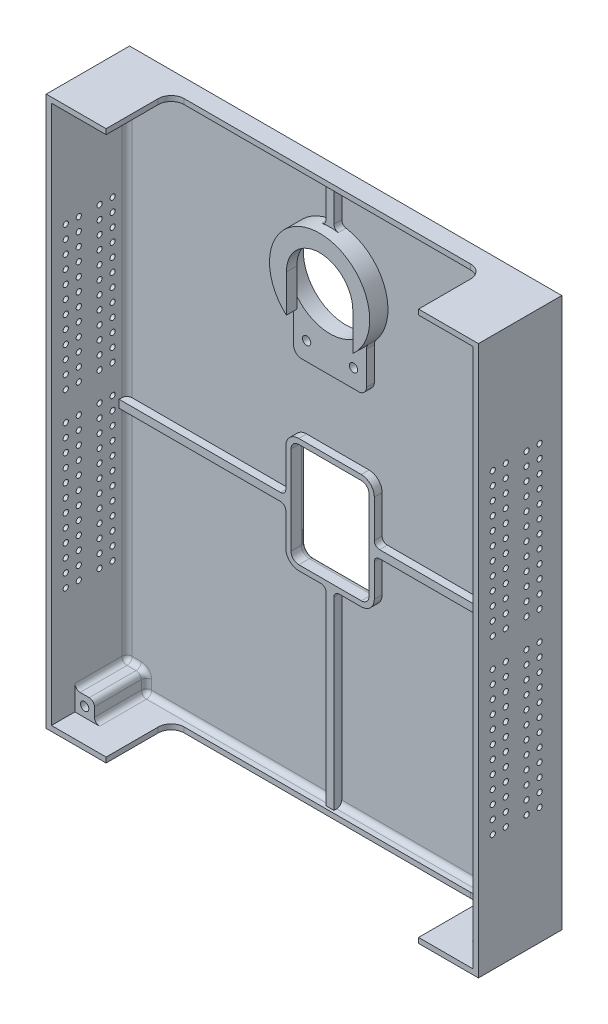
SolidWorks part; units mm, degrees
ref_plane "Front Plane" through (0, 0, 0) normal (0, 0, 1) x (1, 0, 0)
ref_plane "Top Plane" through (0, 0, 0) normal (0, 1, 0) x (1, 0, 0)
ref_plane "Right Plane" through (0, 0, 0) normal (1, 0, 0) x (0, 0, -1)
ref_plane "Plane1" through (0, 0, -1) normal (0, 0, 1) x (1, 0, 0)
sketch "Sketch5" plane through (0, 0, -1) normal (0, 0, 1) x (1, 0, 0)
  line L0 (100, 83.2573) -> (100, -169.2647) construction
  line L2 (17, 83.2573) -> (17, -127.7573)
  line L3 (17, -127.7573) -> (183, -127.7573)
  line L4 (183, 83.2573) -> (183, -127.7573)
  line L5 (17, 83.2573) -> (183, 83.2573)
  circle A0 centre (100, 48.2573) radius 16.25
  point P17 (45, 83.2573)
  dimension "D1" = 166
  dimension "D2" = 83
extrude "Boss-Extrude5" add sketch "Sketch5" along normal blind 3
sketch "Sketch6" plane through (0, 0, 2) normal (0, 0, 1) x (1, 0, 0)
  line L0 (116.25, 48.2573) -> (83.75, 48.2573) construction
  line L2 (86, 35.0451) -> (86, 18.2573)
  line L3 (86, 18.2573) -> (114, 18.2573)
  line L4 (114, 35.0451) -> (114, 18.2573)
  line L5 (100, 48.2573) -> (100, 52.872) construction
  circle A1 centre (100, 48.2573) radius 16.25
  arc A2 (114, 35.0451) -> (86, 35.0451) centre (100, 48.2573) ccw
  circle A6 centre (100, 48.2573) radius 16.25 construction
extrude "Boss-Extrude6" add sketch "Sketch6" along normal blind 3
sketch "Sketch7" plane through (0, 0, 5) normal (0, 0, 1) x (1, 0, 0)
  line L0 (112.75, 33.8351) -> (112.75, 48.2573)
  line L2 (87.25, 48.2573) -> (87.25, 33.8351)
  line L3 (100, 64.5073) -> (100, 48.2573) construction
  line L4 (100, 48.2573) -> (116.25, 48.2573) construction
  arc A8 (112.75, 33.8351) -> (87.25, 33.8351) centre (100, 48.2573) ccw
  circle A9 centre (100, 48.2573) radius 19.25 construction
  circle A10 centre (100, 48.2573) radius 16.25 construction
  circle A12 centre (100, 48.2573) radius 12.75
  arc A13 (112.75, 48.2573) -> (87.25, 48.2573) centre (100, 48.2573) ccw
  dimension "D1" = 1
extrude "Boss-Extrude7" add sketch "Sketch7" along normal blind 4
sketch "Sketch8" plane through (0, 0, 2) normal (0, 0, 1) x (1, 0, 0)
  line L4 (17, -127.7573) -> (183, -127.7573)
  line L5 (183, -127.7573) -> (183, 83.2573)
  line L6 (183, 83.2573) -> (17, 83.2573)
  line L7 (17, 83.2573) -> (17, -127.7573)
  line L8 (17, -127.7573) -> (183, -127.7573)
  line L9 (183, -127.7573) -> (183, 83.2573)
  line L10 (183, 83.2573) -> (17, 83.2573)
  line L11 (17, 83.2573) -> (17, -127.7573)
  line L12 (19, -125.7573) -> (181, -125.7573)
  line L13 (181, -125.7573) -> (181, 81.2573)
  line L14 (181, 81.2573) -> (19, 81.2573)
  line L15 (19, 81.2573) -> (19, -125.7573)
  dimension "D1" = 0
  dimension "D2" = 2
extrude "Boss-Extrude8" add sketch "Sketch8" along normal blind 29
fillet "Fillet2" radius 3 4 edges at (114, 18.2573, 3.5) (114, 35.0451, 3.5) (86, 18.2573, 3.5) (86, 35.0451, 3.5)
sketch "Sketch9" plane through (0, 0, 5) normal (0, 0, 1) x (1, 0, 0)
  line L0 (100, 48.2573) -> (100, 25.2573) construction
  line L1 (91, 25.2573) -> (109, 25.2573) construction
  line L2 (100, 25.2573) -> (100, 23.2329) construction
  circle A0 centre (91, 25.2573) radius 1.6
  circle A1 centre (109, 25.2573) radius 1.6
extrude "Cut-Extrude1" cut sketch "Sketch9" against normal up to surface (6 mm away) up to face at (100, -22.25, -1)
sketch "Sketch12" plane through (183, 0, 0) normal (1, 0, 0) x (0, 0, -1)
  circle A0 centre (-12.5, -16.7427) radius 1
  circle A1 centre (-7.5, -16.7427) radius 1
  circle A2 centre (-7.5, -11.7427) radius 1
  circle A3 centre (-7.5, -6.7427) radius 1
  circle A4 centre (-7.5, -1.7427) radius 1
  circle A5 centre (-7.5, 3.2573) radius 1
  circle A6 centre (-7.5, 8.2573) radius 1
  circle A7 centre (-7.5, 13.2573) radius 1
  circle A8 centre (-7.5, 18.2573) radius 1
  circle A9 centre (-7.5, 23.2573) radius 1
  circle A10 centre (-7.5, 28.2573) radius 1
  circle A11 centre (-7.5, 33.2573) radius 1
  circle A12 centre (-7.5, 38.2573) radius 1
  circle A13 centre (-12.5, -11.7427) radius 1
  circle A14 centre (-12.5, -6.7427) radius 1
  circle A15 centre (-12.5, -1.7427) radius 1
  circle A16 centre (-12.5, 3.2573) radius 1
  circle A17 centre (-12.5, 8.2573) radius 1
  circle A18 centre (-12.5, 13.2573) radius 1
  circle A19 centre (-12.5, 18.2573) radius 1
  circle A20 centre (-12.5, 23.2573) radius 1
  circle A21 centre (-12.5, 28.2573) radius 1
  circle A22 centre (-12.5, 33.2573) radius 1
  circle A23 centre (-12.5, 38.2573) radius 1
  circle A24 centre (-12.5, -82.7573) radius 1
  circle A25 centre (-12.5, -77.7573) radius 1
  circle A26 centre (-12.5, -72.7573) radius 1
  circle A27 centre (-12.5, -67.7573) radius 1
  circle A28 centre (-12.5, -62.7573) radius 1
  circle A29 centre (-12.5, -57.7573) radius 1
  circle A30 centre (-12.5, -52.7573) radius 1
  circle A31 centre (-12.5, -47.7573) radius 1
  circle A32 centre (-12.5, -42.7573) radius 1
  circle A33 centre (-12.5, -37.7573) radius 1
  circle A34 centre (-12.5, -32.7573) radius 1
  circle A35 centre (-7.5, -82.7573) radius 1
  circle A36 centre (-7.5, -77.7573) radius 1
  circle A37 centre (-7.5, -72.7573) radius 1
  circle A38 centre (-7.5, -67.7573) radius 1
  circle A39 centre (-7.5, -62.7573) radius 1
  circle A40 centre (-7.5, -57.7573) radius 1
  circle A41 centre (-7.5, -52.7573) radius 1
  circle A42 centre (-7.5, -47.7573) radius 1
  circle A43 centre (-7.5, -42.7573) radius 1
  circle A44 centre (-7.5, -37.7573) radius 1
  circle A45 centre (-7.5, -32.7573) radius 1
  circle A46 centre (-7.5, -27.7573) radius 1
  circle A47 centre (-12.5, -27.7573) radius 1
  circle A48 centre (-20.5, -27.7573) radius 1
  circle A49 centre (-25.5, -27.7573) radius 1
  circle A50 centre (-25.5, -32.7573) radius 1
  circle A51 centre (-25.5, -37.7573) radius 1
  circle A52 centre (-25.5, -42.7573) radius 1
  circle A53 centre (-25.5, -47.7573) radius 1
  circle A54 centre (-25.5, -52.7573) radius 1
  circle A55 centre (-25.5, -57.7573) radius 1
  circle A56 centre (-25.5, -62.7573) radius 1
  circle A57 centre (-25.5, -67.7573) radius 1
  circle A58 centre (-25.5, -72.7573) radius 1
  circle A59 centre (-25.5, -77.7573) radius 1
  circle A60 centre (-25.5, -82.7573) radius 1
  circle A61 centre (-20.5, -32.7573) radius 1
  circle A62 centre (-20.5, -37.7573) radius 1
  circle A63 centre (-20.5, -42.7573) radius 1
  circle A64 centre (-20.5, -47.7573) radius 1
  circle A65 centre (-20.5, -52.7573) radius 1
  circle A66 centre (-20.5, -57.7573) radius 1
  circle A67 centre (-20.5, -62.7573) radius 1
  circle A68 centre (-20.5, -67.7573) radius 1
  circle A69 centre (-20.5, -72.7573) radius 1
  circle A70 centre (-20.5, -77.7573) radius 1
  circle A71 centre (-20.5, -82.7573) radius 1
  circle A72 centre (-20.5, 38.2573) radius 1
  circle A73 centre (-20.5, 33.2573) radius 1
  circle A74 centre (-20.5, 28.2573) radius 1
  circle A75 centre (-20.5, 23.2573) radius 1
  circle A76 centre (-20.5, 18.2573) radius 1
  circle A77 centre (-20.5, 13.2573) radius 1
  circle A78 centre (-20.5, 8.2573) radius 1
  circle A79 centre (-20.5, 3.2573) radius 1
  circle A80 centre (-20.5, -1.7427) radius 1
  circle A81 centre (-20.5, -6.7427) radius 1
  circle A82 centre (-20.5, -11.7427) radius 1
  circle A83 centre (-25.5, 38.2573) radius 1
  circle A84 centre (-25.5, 33.2573) radius 1
  circle A85 centre (-25.5, 28.2573) radius 1
  circle A86 centre (-25.5, 23.2573) radius 1
  circle A87 centre (-25.5, 18.2573) radius 1
  circle A88 centre (-25.5, 13.2573) radius 1
  circle A89 centre (-25.5, 8.2573) radius 1
  circle A90 centre (-25.5, 3.2573) radius 1
  circle A91 centre (-25.5, -1.7427) radius 1
  circle A92 centre (-25.5, -6.7427) radius 1
  circle A93 centre (-25.5, -11.7427) radius 1
  circle A94 centre (-25.5, -16.7427) radius 1
  circle A95 centre (-20.5, -16.7427) radius 1
  dimension "D1" = 2
  dimension "D2" = 12
extrude "Cut-Extrude4" cut sketch "Sketch12" against normal up to surface (2 mm away) up to face at (181, -22.25, 16.5)
sketch "Sketch13" plane through (0, 0, -1) normal (0, 0, -1) x (-1, 0, 0)
  line L0 (-183, -30.7808) -> (-100, -30.7808) construction
  line L1 (-183, -127.7573) -> (-183, 83.2573) construction
  line L6 (-100, 83.2573) -> (-100, -30.7808) construction
  line L7 (-183, 83.2573) -> (-17, 83.2573) construction
  line L14 (-85, -47.7808) -> (-85, -13.7808)
  line L15 (-88, -10.7808) -> (-112, -10.7808)
  line L16 (-115, -13.7808) -> (-115, -47.7808)
  line L17 (-112, -50.7808) -> (-88, -50.7808)
  circle A1 centre (-100, -30.7808) radius 9 construction
  arc A15 (-88, -50.7808) -> (-85, -47.7808) centre (-88, -47.7808) ccw
  arc A16 (-85, -13.7808) -> (-88, -10.7808) centre (-88, -13.7808) ccw
  arc A17 (-112, -10.7808) -> (-115, -13.7808) centre (-112, -13.7808) ccw
  arc A18 (-115, -47.7808) -> (-112, -50.7808) centre (-112, -47.7808) ccw
extrude "Cut-Extrude5" cut sketch "Sketch13" against normal blind 3
sketch "Sketch14" plane through (17, 0, 0) normal (-1, 0, 0) x (0, 0, 1)
  circle A1 centre (12.5, -82.7573) radius 1
  circle A2 centre (12.5, -82.7573) radius 1
  circle A3 centre (12.5, -16.7427) radius 1
  circle A4 centre (12.5, -16.7427) radius 1
  circle A5 centre (7.5, 18.2573) radius 1
  circle A6 centre (7.5, 18.2573) radius 1
  circle A7 centre (7.5, 13.2573) radius 1
  circle A8 centre (7.5, 13.2573) radius 1
  circle A9 centre (7.5, 8.2573) radius 1
  circle A10 centre (7.5, 8.2573) radius 1
  circle A11 centre (7.5, 3.2573) radius 1
  circle A12 centre (7.5, 3.2573) radius 1
  circle A13 centre (7.5, -1.7427) radius 1
  circle A14 centre (7.5, -1.7427) radius 1
  circle A15 centre (7.5, -6.7427) radius 1
  circle A16 centre (7.5, -6.7427) radius 1
  circle A17 centre (7.5, -11.7427) radius 1
  circle A18 centre (7.5, -11.7427) radius 1
  circle A19 centre (7.5, -16.7427) radius 1
  circle A20 centre (7.5, -16.7427) radius 1
  circle A21 centre (12.5, 3.2573) radius 1
  circle A22 centre (12.5, 3.2573) radius 1
  circle A23 centre (12.5, -1.7427) radius 1
  circle A24 centre (12.5, -1.7427) radius 1
  circle A25 centre (12.5, -6.7427) radius 1
  circle A26 centre (12.5, -6.7427) radius 1
  circle A27 centre (12.5, -11.7427) radius 1
  circle A28 centre (12.5, -11.7427) radius 1
  circle A29 centre (7.5, 38.2573) radius 1
  circle A30 centre (7.5, 38.2573) radius 1
  circle A31 centre (7.5, 33.2573) radius 1
  circle A32 centre (7.5, 33.2573) radius 1
  circle A33 centre (7.5, 28.2573) radius 1
  circle A34 centre (7.5, 28.2573) radius 1
  circle A35 centre (7.5, 23.2573) radius 1
  circle A36 centre (7.5, 23.2573) radius 1
  circle A37 centre (12.5, -77.7573) radius 1
  circle A38 centre (12.5, -77.7573) radius 1
  circle A39 centre (12.5, 38.2573) radius 1
  circle A40 centre (12.5, 38.2573) radius 1
  circle A41 centre (12.5, 33.2573) radius 1
  circle A42 centre (12.5, 33.2573) radius 1
  circle A43 centre (12.5, 28.2573) radius 1
  circle A44 centre (12.5, 28.2573) radius 1
  circle A45 centre (12.5, 23.2573) radius 1
  circle A46 centre (12.5, 23.2573) radius 1
  circle A47 centre (12.5, 18.2573) radius 1
  circle A48 centre (12.5, 18.2573) radius 1
  circle A49 centre (12.5, 13.2573) radius 1
  circle A50 centre (12.5, 13.2573) radius 1
  circle A51 centre (12.5, 8.2573) radius 1
  circle A52 centre (12.5, 8.2573) radius 1
  circle A53 centre (12.5, -37.7573) radius 1
  circle A54 centre (12.5, -37.7573) radius 1
  circle A55 centre (12.5, -42.7573) radius 1
  circle A56 centre (12.5, -42.7573) radius 1
  circle A57 centre (12.5, -47.7573) radius 1
  circle A58 centre (12.5, -47.7573) radius 1
  circle A59 centre (12.5, -52.7573) radius 1
  circle A60 centre (12.5, -52.7573) radius 1
  circle A61 centre (12.5, -57.7573) radius 1
  circle A62 centre (12.5, -57.7573) radius 1
  circle A63 centre (12.5, -62.7573) radius 1
  circle A64 centre (12.5, -62.7573) radius 1
  circle A65 centre (12.5, -67.7573) radius 1
  circle A66 centre (12.5, -67.7573) radius 1
  circle A67 centre (12.5, -72.7573) radius 1
  circle A68 centre (12.5, -72.7573) radius 1
  circle A69 centre (7.5, -52.7573) radius 1
  circle A70 centre (7.5, -52.7573) radius 1
  circle A71 centre (7.5, -57.7573) radius 1
  circle A72 centre (7.5, -57.7573) radius 1
  circle A73 centre (7.5, -62.7573) radius 1
  circle A74 centre (7.5, -62.7573) radius 1
  circle A75 centre (7.5, -67.7573) radius 1
  circle A76 centre (7.5, -67.7573) radius 1
  circle A77 centre (7.5, -72.7573) radius 1
  circle A78 centre (7.5, -72.7573) radius 1
  circle A79 centre (7.5, -77.7573) radius 1
  circle A80 centre (7.5, -77.7573) radius 1
  circle A81 centre (7.5, -82.7573) radius 1
  circle A82 centre (7.5, -82.7573) radius 1
  circle A83 centre (12.5, -32.7573) radius 1
  circle A84 centre (12.5, -32.7573) radius 1
  circle A85 centre (25.5, -27.7573) radius 1
  circle A86 centre (25.5, -27.7573) radius 1
  circle A87 centre (20.5, -27.7573) radius 1
  circle A88 centre (20.5, -27.7573) radius 1
  circle A89 centre (12.5, -27.7573) radius 1
  circle A90 centre (12.5, -27.7573) radius 1
  circle A91 centre (7.5, -27.7573) radius 1
  circle A92 centre (7.5, -27.7573) radius 1
  circle A93 centre (7.5, -32.7573) radius 1
  circle A94 centre (7.5, -32.7573) radius 1
  circle A95 centre (7.5, -37.7573) radius 1
  circle A96 centre (7.5, -37.7573) radius 1
  circle A97 centre (7.5, -42.7573) radius 1
  circle A98 centre (7.5, -42.7573) radius 1
  circle A99 centre (7.5, -47.7573) radius 1
  circle A100 centre (7.5, -47.7573) radius 1
  circle A101 centre (25.5, -67.7573) radius 1
  circle A102 centre (25.5, -67.7573) radius 1
  circle A103 centre (25.5, -62.7573) radius 1
  circle A104 centre (25.5, -62.7573) radius 1
  circle A105 centre (25.5, -57.7573) radius 1
  circle A106 centre (25.5, -57.7573) radius 1
  circle A107 centre (25.5, -52.7573) radius 1
  circle A108 centre (25.5, -52.7573) radius 1
  circle A109 centre (25.5, -47.7573) radius 1
  circle A110 centre (25.5, -47.7573) radius 1
  circle A111 centre (25.5, -42.7573) radius 1
  circle A112 centre (25.5, -42.7573) radius 1
  circle A113 centre (25.5, -37.7573) radius 1
  circle A114 centre (25.5, -37.7573) radius 1
  circle A115 centre (25.5, -32.7573) radius 1
  circle A116 centre (25.5, -32.7573) radius 1
  circle A117 centre (20.5, -52.7573) radius 1
  circle A118 centre (20.5, -52.7573) radius 1
  circle A119 centre (20.5, -47.7573) radius 1
  circle A120 centre (20.5, -47.7573) radius 1
  circle A121 centre (20.5, -42.7573) radius 1
  circle A122 centre (20.5, -42.7573) radius 1
  circle A123 centre (20.5, -37.7573) radius 1
  circle A124 centre (20.5, -37.7573) radius 1
  circle A125 centre (20.5, -32.7573) radius 1
  circle A126 centre (20.5, -32.7573) radius 1
  circle A127 centre (25.5, -82.7573) radius 1
  circle A128 centre (25.5, -82.7573) radius 1
  circle A129 centre (25.5, -77.7573) radius 1
  circle A130 centre (25.5, -77.7573) radius 1
  circle A131 centre (25.5, -72.7573) radius 1
  circle A132 centre (25.5, -72.7573) radius 1
  circle A133 centre (20.5, 33.2573) radius 1
  circle A134 centre (20.5, 33.2573) radius 1
  circle A135 centre (20.5, 38.2573) radius 1
  circle A136 centre (20.5, 38.2573) radius 1
  circle A137 centre (20.5, -82.7573) radius 1
  circle A138 centre (20.5, -82.7573) radius 1
  circle A139 centre (20.5, -77.7573) radius 1
  circle A140 centre (20.5, -77.7573) radius 1
  circle A141 centre (20.5, -72.7573) radius 1
  circle A142 centre (20.5, -72.7573) radius 1
  circle A143 centre (20.5, -67.7573) radius 1
  circle A144 centre (20.5, -67.7573) radius 1
  circle A145 centre (20.5, -62.7573) radius 1
  circle A146 centre (20.5, -62.7573) radius 1
  circle A147 centre (20.5, -57.7573) radius 1
  circle A148 centre (20.5, -57.7573) radius 1
  circle A149 centre (20.5, -6.7427) radius 1
  circle A150 centre (20.5, -6.7427) radius 1
  circle A151 centre (20.5, -1.7427) radius 1
  circle A152 centre (20.5, -1.7427) radius 1
  circle A153 centre (20.5, 3.2573) radius 1
  circle A154 centre (20.5, 3.2573) radius 1
  circle A155 centre (20.5, 8.2573) radius 1
  circle A156 centre (20.5, 8.2573) radius 1
  circle A157 centre (20.5, 13.2573) radius 1
  circle A158 centre (20.5, 13.2573) radius 1
  circle A159 centre (20.5, 18.2573) radius 1
  circle A160 centre (20.5, 18.2573) radius 1
  circle A161 centre (20.5, 23.2573) radius 1
  circle A162 centre (20.5, 23.2573) radius 1
  circle A163 centre (20.5, 28.2573) radius 1
  circle A164 centre (20.5, 28.2573) radius 1
  circle A165 centre (25.5, 8.2573) radius 1
  circle A166 centre (25.5, 8.2573) radius 1
  circle A167 centre (25.5, 13.2573) radius 1
  circle A168 centre (25.5, 13.2573) radius 1
  circle A169 centre (25.5, 18.2573) radius 1
  circle A170 centre (25.5, 18.2573) radius 1
  circle A171 centre (25.5, 23.2573) radius 1
  circle A172 centre (25.5, 23.2573) radius 1
  circle A173 centre (25.5, 28.2573) radius 1
  circle A174 centre (25.5, 28.2573) radius 1
  circle A175 centre (25.5, 33.2573) radius 1
  circle A176 centre (25.5, 33.2573) radius 1
  circle A177 centre (25.5, 38.2573) radius 1
  circle A178 centre (25.5, 38.2573) radius 1
  circle A179 centre (20.5, -11.7427) radius 1
  circle A180 centre (20.5, -11.7427) radius 1
  circle A181 centre (20.5, -16.7427) radius 1
  circle A182 centre (20.5, -16.7427) radius 1
  circle A183 centre (25.5, -16.7427) radius 1
  circle A184 centre (25.5, -16.7427) radius 1
  circle A185 centre (25.5, -11.7427) radius 1
  circle A186 centre (25.5, -11.7427) radius 1
  circle A187 centre (25.5, -6.7427) radius 1
  circle A188 centre (25.5, -6.7427) radius 1
  circle A189 centre (25.5, -1.7427) radius 1
  circle A190 centre (25.5, -1.7427) radius 1
  circle A191 centre (25.5, 3.2573) radius 1
  circle A192 centre (25.5, 3.2573) radius 1
  dimension "D1" = 0
  dimension "D2" = 0
  dimension "D3" = 0
  dimension "D4" = 0
  dimension "D5" = 0
  dimension "D6" = 0
  dimension "D7" = 0
  dimension "D8" = 0
  dimension "D9" = 0
  dimension "D10" = 0
  dimension "D11" = 0
  dimension "D12" = 0
  dimension "D13" = 0
  dimension "D14" = 0
  dimension "D15" = 0
  dimension "D16" = 0
  dimension "D17" = 0
  dimension "D18" = 0
  dimension "D19" = 0
  dimension "D20" = 0
  dimension "D21" = 0
  dimension "D22" = 0
  dimension "D23" = 0
  dimension "D24" = 0
  dimension "D25" = 0
  dimension "D26" = 0
  dimension "D27" = 0
  dimension "D28" = 0
  dimension "D29" = 0
  dimension "D30" = 0
  dimension "D31" = 0
  dimension "D32" = 0
  dimension "D33" = 0
  dimension "D34" = 0
  dimension "D35" = 0
  dimension "D36" = 0
  dimension "D37" = 0
  dimension "D38" = 0
  dimension "D39" = 0
  dimension "D40" = 0
  dimension "D41" = 0
  dimension "D42" = 0
  dimension "D43" = 0
  dimension "D44" = 0
  dimension "D45" = 0
  dimension "D46" = 0
  dimension "D47" = 0
  dimension "D48" = 0
  dimension "D49" = 0
  dimension "D50" = 0
  dimension "D51" = 0
  dimension "D52" = 0
  dimension "D53" = 0
  dimension "D54" = 0
  dimension "D55" = 0
  dimension "D56" = 0
  dimension "D57" = 0
  dimension "D58" = 0
  dimension "D59" = 0
  dimension "D60" = 0
  dimension "D61" = 0
  dimension "D62" = 0
  dimension "D63" = 0
  dimension "D64" = 0
  dimension "D65" = 0
  dimension "D66" = 0
  dimension "D67" = 0
  dimension "D68" = 0
  dimension "D69" = 0
  dimension "D70" = 0
  dimension "D71" = 0
  dimension "D72" = 0
  dimension "D73" = 0
  dimension "D74" = 0
  dimension "D75" = 0
  dimension "D76" = 0
  dimension "D77" = 0
  dimension "D78" = 0
  dimension "D79" = 0
  dimension "D80" = 0
  dimension "D81" = 0
  dimension "D82" = 0
  dimension "D83" = 0
  dimension "D84" = 0
  dimension "D85" = 0
  dimension "D86" = 0
  dimension "D87" = 0
  dimension "D88" = 0
  dimension "D89" = 0
  dimension "D90" = 0
  dimension "D91" = 0
  dimension "D92" = 0
  dimension "D93" = 0
  dimension "D94" = 0
  dimension "D95" = 0
  dimension "D96" = 0
extrude "Cut-Extrude6" cut sketch "Sketch14" against normal up to surface (2 mm away) up to face at (19, -22.25, 16.5)
sketch "Sketch15" plane through (0, -127.7573, 0) normal (0, -1, 0) x (1, 0, 0)
  line L5 (100, -1) -> (100, 31) construction
  line L6 (17, -1) -> (183, -1) construction
  line L7 (17, 31) -> (183, 31) construction
  line L8 (40, 31) -> (160, 31)
  line L9 (40, 31) -> (40, 11)
  line L10 (45, 6) -> (155, 6)
  line L11 (160, 31) -> (160, 11)
  arc A4 (155, 6) -> (160, 11) centre (155, 11) ccw
  arc A5 (40, 11) -> (45, 6) centre (45, 11) ccw
  point P12 (160, 6)
  point P15 (40, 6)
  dimension "D4" = 5
  dimension "D1" = 60
  dimension "D2" = 120
  dimension "D3" = 25
extrude "Cut-Extrude7" cut sketch "Sketch15" against normal up to surface (2 mm away) up to face at (100, -125.7573, 16.5)
sketch "Sketch16" plane through (0, 83.2573, 0) normal (0, 1, 0) x (1, 0, 0)
  line L4 (40, -31) -> (160, -31)
  line L5 (40, -31) -> (160, -31)
  line L6 (160, -31) -> (160, -11)
  line L7 (160, -31) -> (160, -11)
  line L12 (155, -6) -> (45, -6)
  line L13 (155, -6) -> (45, -6)
  line L14 (40, -11) -> (40, -31)
  line L15 (40, -11) -> (40, -31)
  arc A2 (160, -11) -> (155, -6) centre (155, -11) ccw
  arc A3 (160, -11) -> (155, -6) centre (155, -11) ccw
  arc A4 (45, -6) -> (40, -11) centre (45, -11) ccw
  arc A5 (45, -6) -> (40, -11) centre (45, -11) ccw
  dimension "D1" = 0
extrude "Cut-Extrude8" cut sketch "Sketch16" against normal up to surface (2 mm away) up to face at (100, 81.2573, 16.5)
sketch "Sketch18" plane through (0, 0, 2) normal (0, 0, 1) x (1, 0, 0)
  line L1 (19, -125.7573) -> (26.5, -125.7573)
  line L2 (19, -125.7573) -> (19, -118.2573)
  line L3 (19, -118.2573) -> (26.5, -118.2573)
  line L4 (26.5, -125.7573) -> (26.5, -118.2573)
  line L5 (181, -125.7573) -> (173.5, -125.7573)
  line L6 (181, -125.7573) -> (181, -118.2573)
  line L7 (181, -118.2573) -> (173.5, -118.2573)
  line L8 (173.5, -125.7573) -> (173.5, -118.2573)
  line L9 (19, 81.2573) -> (26.5, 81.2573)
  line L10 (19, 81.2573) -> (19, 73.7573)
  line L11 (19, 73.7573) -> (26.5, 73.7573)
  line L12 (26.5, 81.2573) -> (26.5, 73.7573)
  line L13 (181, 81.2573) -> (173.5, 81.2573)
  line L14 (181, 81.2573) -> (181, 73.7573)
  line L15 (181, 73.7573) -> (173.5, 73.7573)
  line L16 (173.5, 81.2573) -> (173.5, 73.7573)
extrude "Boss-Extrude10" add sketch "Sketch18" along normal blind 20
fillet "Fillet3" radius 2 12 edges at (181, 73.7573, 12) (173.5, 73.7573, 12) (173.5, 81.2573, 12) (26.5, 81.2573, 12) (26.5, 73.7573, 12) (19, 73.7573, 12) (19, -118.2573, 12) (26.5, -118.2573, 12) (26.5, -125.7573, 12) (181, -118.2573, 12) (173.5, -118.2573, 12) (173.5, -125.7573, 12)
sketch "Sketch19" plane through (0, 0, 22) normal (0, 0, 1) x (1, 0, 0)
  line L4 (100, -127.7573) -> (100, 83.2573) construction
  line L5 (45, -127.7573) -> (155, -127.7573) construction
  line L6 (155, 83.2573) -> (45, 83.2573) construction
  line L7 (100, -22.25) -> (17, -22.25) construction
  line L8 (17, 83.2573) -> (17, -127.7573) construction
  circle A0 centre (22.75, -122.0073) radius 1.6
  circle A1 centre (177.25, -122.0073) radius 1.6
  circle A2 centre (177.25, 77.5073) radius 1.6
  circle A3 centre (22.75, 77.5073) radius 1.6
extrude "Cut-Extrude9" cut sketch "Sketch19" against normal up to surface (23 mm away) up to face at (100, -30.7808, -1)
fillet "Fillet4" radius 2 24 edges at (180.4142, -117.6715, 2) (177.25, -118.2573, 2) (174.0858, -118.8431, 2) (173.5, -122.0073, 2) (172.9142, -125.1715, 2) (100, -125.7573, 2) (27.0858, -125.1715, 2) (26.5, -122.0073, 2) (25.9142, -118.8431, 2) (22.75, -118.2573, 2) (19.5858, -117.6715, 2) (19, -22.25, 2) (19.5858, 73.1715, 2) (22.75, 73.7573, 2) (25.9142, 74.3431, 2) (26.5, 77.5073, 2) (27.0858, 80.6715, 2) (100, 81.2573, 2) (172.9142, 80.6715, 2) (173.5, 77.5073, 2) (174.0858, 74.3431, 2) (177.25, 73.7573, 2) (180.4142, 73.1715, 2) (181, -22.25, 2)
sketch "Sketch20" plane through (0, 0, 2) normal (0, 0, 1) x (1, 0, 0)
  line L0 (83, -30.2573) -> (83, -13.7808)
  line L1 (155, 83.2573) -> (45, 83.2573) construction
  line L2 (45, -127.7573) -> (155, -127.7573) construction
  line L3 (88, -10.7808) -> (112, -10.7808) construction
  line L4 (101.5, -127.7573) -> (98.5, -127.7573)
  line L5 (101.5, -127.7573) -> (101.5, -52.7808)
  line L6 (101.5, 83.2573) -> (98.5, 83.2573)
  line L7 (98.5, -127.7573) -> (98.5, -52.7808)
  line L8 (115, -13.7808) -> (115, -47.7808) construction
  line L9 (112, -50.7808) -> (88, -50.7808) construction
  line L10 (85, -47.7808) -> (85, -13.7808) construction
  line L11 (88, -10.7808) -> (112, -10.7808)
  line L12 (115, -13.7808) -> (115, -47.7808)
  line L13 (112, -50.7808) -> (88, -50.7808)
  line L14 (85, -47.7808) -> (85, -13.7808)
  line L15 (88, -8.7808) -> (112, -8.7808)
  line L16 (117, -13.7808) -> (117, -30.2573)
  line L17 (112, -52.7808) -> (101.5, -52.7808)
  line L18 (83, -47.7808) -> (83, -33.2573)
  line L20 (183, -127.7573) -> (183, 83.2573) construction
  line L21 (183, -33.2573) -> (117, -33.2573)
  line L22 (183, -33.2573) -> (183, -30.2573)
  line L23 (183, -30.2573) -> (117, -30.2573)
  line L24 (17, -33.2573) -> (17, -30.2573)
  line L25 (17, 83.2573) -> (17, -127.7573) construction
  line L26 (83, -33.2573) -> (17, -33.2573)
  line L28 (98.5, -52.7808) -> (88, -52.7808)
  line L31 (83, -30.2573) -> (17, -30.2573)
  line L33 (112, -52.7808) -> (88, -52.7808) construction
  line L35 (117, -33.2573) -> (117, -47.7808)
  line L38 (117, -13.7808) -> (117, -47.7808) construction
  line L39 (88, -8.7808) -> (112, -8.7808) construction
  line L40 (83, -47.7808) -> (83, -13.7808) construction
  line L44 (98.5, 64.4379) -> (98.5, 83.2573)
  line L45 (101.5, 64.4379) -> (101.5, 83.2573)
  line L49 (112.75, 48.2573) -> (112.75, 38.1826)
  line L51 (87.25, 38.1826) -> (87.25, 48.2573)
  arc A0 (88, -10.7808) -> (85, -13.7808) centre (88, -13.7808) ccw construction
  arc A1 (115, -13.7808) -> (112, -10.7808) centre (112, -13.7808) ccw construction
  arc A2 (112, -50.7808) -> (115, -47.7808) centre (112, -47.7808) ccw construction
  arc A3 (85, -47.7808) -> (88, -50.7808) centre (88, -47.7808) ccw construction
  arc A4 (88, -10.7808) -> (85, -13.7808) centre (88, -13.7808) ccw
  arc A5 (115, -13.7808) -> (112, -10.7808) centre (112, -13.7808) ccw
  arc A6 (112, -50.7808) -> (115, -47.7808) centre (112, -47.7808) ccw
  arc A7 (85, -47.7808) -> (88, -50.7808) centre (88, -47.7808) ccw
  arc A8 (117, -13.7808) -> (112, -8.7808) centre (112, -13.7808) ccw
  arc A9 (112, -52.7808) -> (117, -47.7808) centre (112, -47.7808) ccw
  arc A10 (83, -47.7808) -> (88, -52.7808) centre (88, -47.7808) ccw
  arc A11 (88, -8.7808) -> (83, -13.7808) centre (88, -13.7808) ccw
  arc A14 (112.75, 48.2573) -> (87.25, 48.2573) centre (100, 48.2573) ccw
  arc A15 (112.75, 38.1826) -> (87.25, 38.1826) centre (100, 48.2573) ccw
  arc A18 (101.5, 64.4379) -> (98.5, 64.4379) centre (100, 48.2573) ccw
  point P0 (111.5893, -8.7808)
  dimension "D1" = 0
  dimension "D3" = 2
extrude "Boss-Extrude11" add sketch "Sketch20" along normal blind 3
fillet "Fillet5" radius 2 8 edges at (98.5, -52.7808, 3.5) (101.5, -52.7808, 3.5) (117, -33.2573, 3.5) (117, -30.2573, 3.5) (83, -33.2573, 3.5) (83, -30.2573, 3.5) (101.5, 67.4488, 3.5) (98.5, 67.4488, 3.5)
sketch "Sketch21" plane through (0, 0, -1) normal (0, 0, -1) x (-1, 0, 0)
  circle A0 centre (-109, 25.2573) radius 2.25
  circle A1 centre (-91, 25.2573) radius 2.25
extrude "Cut-Extrude10" cut sketch "Sketch21" against normal blind 3
fillet "Fillet6" radius 2 8 edges at (85.8787, -49.9021, -1) (100, -50.7808, -1) (114.1213, -49.9021, -1) (115, -30.7808, -1) (114.1213, -11.6594, -1) (100, -10.7808, -1) (85.8787, -11.6594, -1) (85, -30.7808, -1)
chamfer "Chamfer1" distance 1.5 angle 45 4 edges at (21.15, 77.5073, -1) (21.15, -122.0073, -1) (175.65, -122.0073, -1) (175.65, 77.5073, -1)
